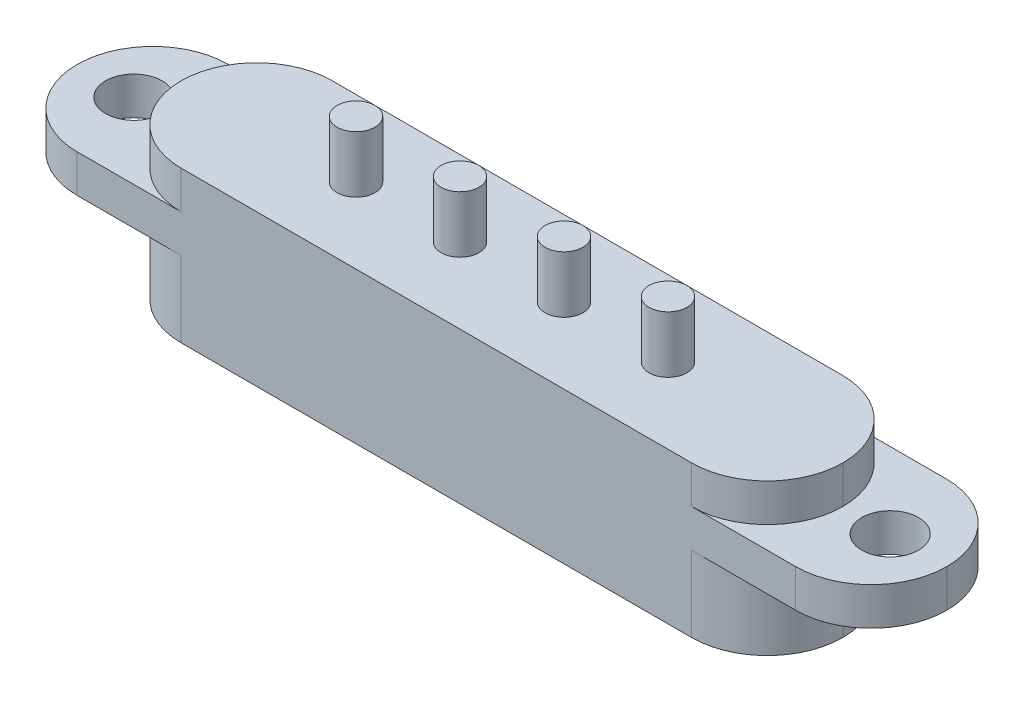
SolidWorks part; units mm, degrees
ref_plane "Front Plane" through (0, 0, 0) normal (0, 0, 1) x (1, 0, 0)
ref_plane "Top Plane" through (0, 0, 0) normal (0, 1, 0) x (1, 0, 0)
ref_plane "Right Plane" through (0, 0, 0) normal (1, 0, 0) x (0, 0, -1)
sketch "Sketch1" plane through (0, 0, 0) normal (0, 1, 0) x (1, 0, 0)
  line L1 (0, 0) -> (23, 0)
  line L2 (0, 0) -> (0, -4)
  line L3 (0, -4) -> (23, -4)
  line L4 (23, 0) -> (23, -4)
  circle A0 centre (1.5, -2) radius 0.75
  circle A1 centre (21.5, -2) radius 0.75
  dimension "D3" = 1.5
  dimension "D4" = 1.5
  dimension "D1" = 4
  dimension "D2" = 23
  dimension "D5" = 20
  dimension "D6" = 1.5
  dimension "D7" = 2
  dimension "D8" = 2
extrude "Boss-Extrude1" add sketch "Sketch1" along normal blind 1
sketch "Sketch2" plane through (0, 1, 0) normal (0, 1, 0) x (1, 0, 0)
  line L0 (23, 0) -> (0, 0) construction
  line L1 (2.75, 0) -> (20.25, 0)
  line L2 (2.75, 0) -> (2.75, -4)
  line L3 (2.75, -4) -> (20.25, -4)
  line L4 (20.25, 0) -> (20.25, -4)
  line L5 (0, -4) -> (23, -4) construction
  line L6 (0, 0) -> (0, -4) construction
  dimension "D1" = 17.5
  dimension "D2" = 2.75
extrude "Boss-Extrude2" add sketch "Sketch2" along normal blind 1
sketch "Sketch3" plane through (0, 0, 0) normal (0, -1, 0) x (-1, 0, 0)
  line L0 (0, -4) -> (-23, -4) construction
  line L1 (-2.75, -4) -> (-20.25, -4)
  line L2 (-2.75, -4) -> (-2.75, 0)
  line L3 (-2.75, 0) -> (-20.25, 0)
  line L4 (-20.25, -4) -> (-20.25, 0)
  line L5 (-23, 0) -> (0, 0) construction
  line L6 (-23, -4) -> (-23, 0) construction
  dimension "D1" = 17.5
  dimension "D2" = 2.75
extrude "Boss-Extrude3" add sketch "Sketch3" along normal blind 2
sketch "Sketch4" plane through (0, 2, 0) normal (0, 1, 0) x (1, 0, 0)
  line L0 (2.75, -4) -> (20.25, -4) construction
  line L1 (2.75, 0) -> (2.75, -4) construction
  circle A0 centre (7.375, -2) radius 0.5
  circle A1 centre (10.125, -2) radius 0.5
  circle A2 centre (12.875, -2) radius 0.5
  circle A3 centre (15.625, -2) radius 0.5
  dimension "D7" = 2
  dimension "D8" = 2
  dimension "D1" = 1
  dimension "D2" = 1
  dimension "D3" = 1
  dimension "D4" = 1
  dimension "D9" = 2.75
  dimension "D10" = 2.75
  dimension "D11" = 2.75
  dimension "D12" = 4.625
extrude "Boss-Extrude4" add sketch "Sketch4" along normal blind 1.5
fillet "Fillet1" radius 2 8 edges at (20.25, -1, 4) (20.25, -1, 0) (20.25, 1.5, 0) (20.25, 1.5, 4) (2.75, 1.5, 4) (2.75, 1.5, 0) (2.75, -1, 0) (2.75, -1, 4)
fillet "Fillet2" radius 2 4 edges at (0, 0.5, 4) (0, 0.5, 0) (23, 0.5, 0) (23, 0.5, 4)
equation "\"D2@Sketch1\"=20+3"
equation "\"D2@Sketch2\"=23/2-17.5/2"
equation "\"D2@Sketch3\"=23/2-17.5/2"
equation "\"D10@Sketch4\"=\"D9@Sketch4\""
equation "\"D11@Sketch4\"=\"D10@Sketch4\""
equation "\"D12@Sketch4\"=17.5/2-2.75*3/2"
